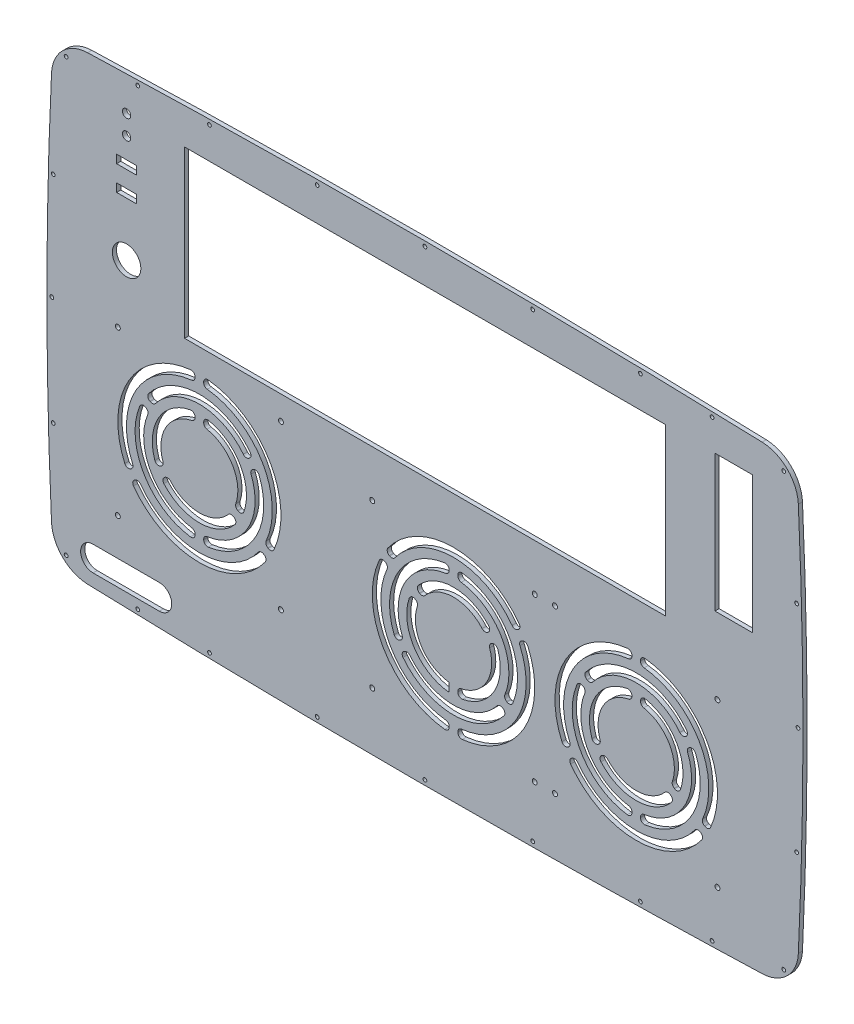
SolidWorks part; units mm, degrees
ref_plane "Front" through (0, 0, 0) normal (0, 0, 1) x (1, 0, 0)
ref_plane "Top" through (0, 0, 0) normal (0, 1, 0) x (1, 0, 0)
ref_plane "Right" through (0, 0, 0) normal (1, 0, 0) x (0, 0, -1)
sketch "Sketch1" plane through (0, 0, 0) normal (0, 0, 1) x (1, 0, 0)
  line L0 (79.622, -180.7786) -> (85.5592, -180.7149)
  line L1 (223.1034, -177.9577) -> (258.4236, -176.8528)
  circle A0 centre (-274.9542, -165.9116) radius 1.435
  arc A93 (-279.7814, -166.2105) -> (-275.1845, -170.7425) centre (-257.4604, -148.1676) ccw
  arc A94 (275.1845, -170.7425) -> (279.7814, -166.2105) centre (257.4604, -148.1676) ccw
  circle A100 centre (-274.9542, 164.9337) radius 1.4351
  circle A101 centre (-284.8103, 82.061) radius 1.4351
  circle A102 centre (-285.9024, 0) radius 1.4351
  circle A103 centre (-284.8103, -83.0389) radius 1.4351
  arc A104 (-258.4236, -176.8528) -> (-223.1034, -177.9577) centre (0, 7519.4009) ccw
  circle A105 centre (-220.0271, -174.2607) radius 1.4351
  circle A106 centre (-165.1, -175.6347) radius 1.4351
  arc A107 (-162.2131, -179.4816) -> (-85.5592, -180.7149) centre (0, 7519.4009) ccw
  arc A108 (-168.1492, -179.3542) -> (-162.2131, -179.4816) centre (0, 7519.4009) ccw
  circle A109 centre (-82.55, -176.963) radius 1.4351
  circle A110 centre (0, -177.4057) radius 1.4351
  circle A111 centre (82.55, -176.963) radius 1.4351
  circle A112 centre (165.1, -175.6347) radius 1.4351
  circle A113 centre (220.0271, -174.2607) radius 1.4351
  circle A114 centre (284.8103, -83.0389) radius 1.4351
  circle A115 centre (285.9024, 0) radius 1.4351
  circle A116 centre (284.8103, 82.061) radius 1.4351
  circle A117 centre (274.9542, 164.9337) radius 1.4351
  circle A118 centre (220.0271, 173.2828) radius 1.4351
  circle A119 centre (165.1, 174.6568) radius 1.4351
  circle A120 centre (82.55, 175.9851) radius 1.4351
  circle A121 centre (0, 176.4278) radius 1.4351
  circle A122 centre (-82.55, 175.9851) radius 1.4351
  circle A123 centre (-220.0271, 173.2828) radius 1.4351
  circle A124 centre (-165.1, 174.6568) radius 1.4351
  arc A125 (-162.2131, 178.5037) -> (-168.1492, 178.3763) centre (0, -7520.3788) ccw
  arc A126 (-85.5592, 179.737) -> (-162.2131, 178.5037) centre (0, -7520.3788) ccw
  arc A127 (-79.622, 179.8007) -> (-85.5592, 179.737) centre (0, -7520.3788) ccw
  arc A128 (-2.9688, 180.2118) -> (-79.622, 179.8007) centre (0, -7520.3788) ccw
  arc A129 (2.9688, 180.2118) -> (-2.9688, 180.2118) centre (0, -7520.3788) ccw
  arc A130 (79.622, 179.8007) -> (2.9688, 180.2118) centre (0, -7520.3788) ccw
  arc A131 (85.5592, 179.737) -> (79.622, 179.8007) centre (0, -7520.3788) ccw
  arc A132 (162.2131, 178.5037) -> (85.5592, 179.737) centre (0, -7520.3788) ccw
  arc A133 (168.1492, 178.3763) -> (162.2131, 178.5037) centre (0, -7520.3788) ccw
  arc A134 (217.1671, 177.1496) -> (168.1492, 178.3763) centre (0, -7520.3788) ccw
  arc A135 (223.1034, 176.9798) -> (217.1671, 177.1496) centre (0, -7520.3788) ccw
  arc A136 (258.4236, 175.8749) -> (223.1034, 176.9798) centre (0, -7520.3788) ccw
  arc A137 (275.1845, 169.7646) -> (258.4236, 175.8749) centre (257.4604, 147.1897) ccw
  arc A138 (279.7814, 165.2326) -> (275.1845, 169.7646) centre (257.4604, 147.1897) ccw
  arc A139 (286.1291, 148.559) -> (279.7814, 165.2326) centre (257.4604, 147.1897) ccw
  arc A140 (288.513, 85.1308) -> (286.1291, 148.559) centre (-2834.64, -0.4889) ccw
  arc A141 (288.6701, 79.1915) -> (288.513, 85.1308) centre (-2834.64, -0.4889) ccw
  arc A142 (289.6845, 2.9713) -> (288.6701, 79.1915) centre (-2834.64, -0.4889) ccw
  arc A143 (289.6854, -2.9701) -> (289.6845, 2.9713) centre (-2834.64, -0.4889) ccw
  arc A144 (288.6701, -80.1694) -> (289.6854, -2.9701) centre (-2834.64, -0.4889) ccw
  arc A145 (288.513, -86.1087) -> (288.6701, -80.1694) centre (-2834.64, -0.4889) ccw
  arc A146 (286.1291, -149.5369) -> (288.513, -86.1087) centre (-2834.64, -0.4889) ccw
  arc A147 (279.7814, -166.2105) -> (286.1291, -149.5369) centre (257.4604, -148.1676) ccw
  arc A148 (275.1845, -170.7425) -> (279.7814, -166.2105) centre (257.4604, -148.1676) ccw
  arc A149 (258.4236, -176.8528) -> (275.1845, -170.7425) centre (257.4604, -148.1676) ccw
  arc A150 (217.1671, -178.1275) -> (223.1034, -177.9577) centre (0, 7519.4009) ccw
  arc A151 (168.1492, -179.3542) -> (217.1671, -178.1275) centre (0, 7519.4009) ccw
  arc A152 (85.5592, -180.7149) -> (162.2131, -179.4816) centre (0, 7519.4009) ccw
  arc A153 (162.2131, -179.4816) -> (168.1492, -179.3542) centre (0, 7519.4009) ccw
  arc A154 (2.9688, -181.1897) -> (79.622, -180.7786) centre (0, 7519.4009) ccw
  arc A155 (-2.9688, -181.1897) -> (2.9688, -181.1897) centre (0, 7519.4009) ccw
  arc A156 (-79.622, -180.7786) -> (-2.9688, -181.1897) centre (0, 7519.4009) ccw
  arc A157 (-85.5592, -180.7149) -> (-79.622, -180.7786) centre (0, 7519.4009) ccw
  arc A158 (-217.1671, -178.1275) -> (-168.1492, -179.3542) centre (0, 7519.4009) ccw
  arc A159 (-223.1034, -177.9577) -> (-217.1671, -178.1275) centre (0, 7519.4009) ccw
  arc A160 (-275.1845, -170.7425) -> (-258.4236, -176.8528) centre (-257.4604, -148.1676) ccw
  arc A161 (-279.7814, -166.2105) -> (-275.1845, -170.7425) centre (-257.4604, -148.1676) ccw
  arc A162 (-286.1291, -149.5369) -> (-279.7814, -166.2105) centre (-257.4604, -148.1676) ccw
  arc A163 (-288.513, -86.1087) -> (-286.1291, -149.5369) centre (2834.64, -0.4889) ccw
  arc A164 (-288.6701, -80.1694) -> (-288.513, -86.1087) centre (2834.64, -0.4889) ccw
  arc A165 (-289.6854, -2.9701) -> (-288.6701, -80.1694) centre (2834.64, -0.4889) ccw
  arc A166 (-289.6845, 2.9713) -> (-289.6854, -2.9701) centre (2834.64, -0.4889) ccw
  arc A167 (-288.6701, 79.1915) -> (-289.6845, 2.9713) centre (2834.64, -0.4889) ccw
  arc A168 (-288.513, 85.1308) -> (-288.6701, 79.1915) centre (2834.64, -0.4889) ccw
  arc A169 (-286.1291, 148.559) -> (-288.513, 85.1308) centre (2834.64, -0.4889) ccw
  arc A170 (-279.7814, 165.2326) -> (-286.1291, 148.559) centre (-257.4604, 147.1897) ccw
  arc A171 (-275.1845, 169.7646) -> (-279.7814, 165.2326) centre (-257.4604, 147.1897) ccw
  arc A172 (-258.4236, 175.8749) -> (-275.1845, 169.7646) centre (-257.4604, 147.1897) ccw
  arc A173 (-223.1034, 176.9798) -> (-258.4236, 175.8749) centre (0, -7520.3788) ccw
  arc A174 (-217.1671, 177.1496) -> (-223.1034, 176.9798) centre (0, -7520.3788) ccw
  arc A175 (-168.1492, 178.3763) -> (-217.1671, 177.1496) centre (0, -7520.3788) ccw
  circle A176 centre (274.9542, -165.9116) radius 1.4351
extrude "Boss-Extrude1" add sketch "Sketch1" along normal blind 3.175 contours A125 A175 A174 A173 A172 A171 A170 A169 A168 A167 A166 A165 A164 A163 A162 A160 A104 A159 A158 A108 A107 A157 A156 A155 A154 L0 A152 A153 A151 A150 L1 A149 A147 A146 A145 A144 A143 A142 A141 A140 A139 region at (-0.0006, -0.4886, 0)
sketch "Sketch2" plane through (0, 0, 3.175) normal (0, 0, 1) x (1, 0, 0)
  line L0 (-184.15, 150.4749) -> (-184.15, 23.4749)
  line L1 (184.15, 23.4749) -> (-184.15, 23.4749)
  line L2 (184.15, 23.4749) -> (184.15, 150.4749)
  line L3 (184.15, 150.4749) -> (-184.15, 150.4749)
  line L4 (0, 23.4749) -> (0, 150.4749) construction
  line L5 (0, -177.4057) -> (0, 176.4278) construction
  arc A0 (258.4236, 175.8749) -> (-258.4236, 175.8749) centre (0, -7520.3788) ccw construction
  arc A1 (258.4236, 175.8749) -> (-258.4236, 175.8749) centre (0, -7520.3788) ccw
  dimension "D1" = 25.4
  dimension "D3" = 127
  dimension "D4" = 368.3
extrude "Cut-Extrude1" cut sketch "Sketch2" against normal through all contours L2 L3 L0 L1 region at (0, 86.9749, 3.175)
sketch "Sketch4" plane through (212.7609, -112.7514, 0) normal (0, 0, -1) x (0, -1, 0)
  circle A0 centre (-100.5499, 253.1068) radius 1.8986
  circle A1 centre (23.9501, 253.1068) radius 1.8987
  circle A2 centre (-100.5499, 128.6068) radius 1.8987
  circle A3 centre (-100.5499, 113.1068) radius 1.8987
  circle A4 centre (23.9501, 128.6068) radius 1.8987
  circle A5 centre (23.9501, 113.1068) radius 1.8987
  circle A6 centre (-100.5499, -11.3932) radius 1.8987
  circle A7 centre (23.9501, -11.3932) radius 1.8987
  circle A8 centre (53.1601, -62.1932) radius 1.4351 construction
  circle A10 centre (53.1601, -62.1932) radius 1.4351 construction
  dimension "D7" = 3.7973
  dimension "D1" = 124.5
  dimension "D2" = 124.5
  dimension "D3" = 140
  dimension "D4" = 264.5
  dimension "D5" = 29.21
  dimension "D6" = 50.8
extrude "Cut-Extrude2" cut sketch "Sketch4" against normal through all
sketch "Sketch5" plane through (0, 0, 0) normal (0, 0, -1) x (-1, 0, 0)
  circle A0 centre (235.3291, -119.7028) radius 1.8987
  circle A1 centre (110.3291, -119.7028) radius 1.8987
  circle A2 centre (110.3291, 5.2972) radius 1.8987
  circle A3 centre (235.3291, 5.2972) radius 1.8987
  dimension "D1" = 3.7973
  dimension "D4" = 50.8
  dimension "D2" = 125
  dimension "D3" = 125
  dimension "D5" = 57.15
extrude "Cut-Extrude3" cut sketch "Sketch5" against normal through all
sketch "Sketch6" plane through (0, 0, 0) normal (0, 0, -1) x (-1, 0, 0)
  line L1 (184.15, 150.4749) -> (184.15, 23.4749) construction
  line L2 (-184.15, 150.4749) -> (184.15, 150.4749) construction
  line L3 (220.98, 119.6647) -> (236.22, 119.6647)
  line L4 (220.98, 119.6647) -> (220.98, 113.3147)
  line L5 (220.98, 113.3147) -> (236.22, 113.3147)
  line L6 (236.22, 119.6647) -> (236.22, 113.3147)
  line L7 (220.98, 119.6647) -> (236.22, 113.3147) construction
  line L8 (220.98, 113.3147) -> (236.22, 119.6647) construction
  line L9 (220.98, 100.6147) -> (236.22, 100.6147)
  line L10 (220.98, 100.6147) -> (220.98, 94.2647)
  line L11 (220.98, 94.2647) -> (236.22, 94.2647)
  line L12 (236.22, 100.6147) -> (236.22, 94.2647)
  line L13 (220.98, 100.6147) -> (236.22, 94.2647) construction
  line L14 (220.98, 94.2647) -> (236.22, 100.6147) construction
  line L15 (-250.825, 150.4749) -> (-222.25, 150.4749)
  line L16 (-250.825, 150.4749) -> (-250.825, 45.6999)
  line L17 (-250.825, 45.6999) -> (-222.25, 45.6999)
  line L18 (-222.25, 150.4749) -> (-222.25, 45.6999)
  line L19 (-184.15, 23.4749) -> (-184.15, 150.4749) construction
  circle A0 centre (228.6, 150.4749) radius 3.175
  circle A1 centre (228.6, 135.5397) radius 3.175
  point P4 (228.6, 97.4397)
  point P12 (228.6, 116.4897)
  dimension "D1" = 6.35
  dimension "D8" = 104.775
  dimension "D2" = 14.9352
  dimension "D3" = 44.45
  dimension "D4" = 19.05
  dimension "D5" = 19.05
  dimension "D6" = 6.35
  dimension "D7" = 15.24
  dimension "D9" = 28.575
  dimension "D10" = 38.1
extrude "Cut-Extrude4" cut sketch "Sketch6" against normal through all contours L16 L15 L18 L17 | L4 L3 L6 L5 | A1 | A0 | L10 L9 L12 L11
sketch "Sketch7" plane through (0, 0, 0) normal (0, 0, -1) x (-1, 0, 0)
  line L0 (220.98, 94.2647) -> (236.22, 94.2647) construction
  circle A0 centre (228.6, 52.9897) radius 10.922
  point P2 (228.6, 135.5397)
  dimension "D1" = 21.844
  dimension "D2" = 41.275
extrude "Cut-Extrude5" cut sketch "Sketch7" against normal through all contours A0
sketch "Sketch8" plane through (0, 0, 0) normal (0, 0, -1) x (-1, 0, 0)
  line L0 (-224.1542, -12.2016) -> (-99.6542, -12.2016) construction
  line L1 (-84.1542, -12.2016) -> (40.3458, -12.2016) construction
  line L2 (40.3458, -12.2016) -> (40.3458, -136.7016) construction
  line L3 (-161.9042, -12.2016) -> (-161.9042, -18.8056) construction
  line L4 (-165.2062, -12.2892) -> (-165.2062, -18.9036)
  line L5 (-158.6022, -12.2892) -> (-158.6022, -18.9036)
  line L6 (-125.1518, -53.2326) -> (-119.4325, -49.9306) construction
  line L7 (-121.1799, -47.1266) -> (-126.9142, -50.4373)
  line L8 (-117.8779, -52.8458) -> (-123.6122, -56.1565)
  line L9 (-136.5902, -89.0666) -> (-130.871, -92.3686) construction
  line L10 (-129.352, -89.4327) -> (-135.1013, -86.1134)
  line L11 (-132.654, -95.152) -> (-138.4033, -91.8326)
  line L12 (-106.419, -102.6731) -> (-112.1472, -99.3659)
  line L13 (-107.9941, -105.5766) -> (-113.7133, -102.2746) construction
  line L14 (-109.721, -108.3924) -> (-115.4492, -105.0852)
  line L15 (-158.6022, -123.3823) -> (-158.6022, -116.7609)
  line L16 (-161.9042, -116.8896) -> (-161.9042, -123.4936) construction
  line L17 (-165.2062, -123.3823) -> (-165.2062, -116.7609)
  line L18 (-191.1543, -95.152) -> (-185.405, -91.8326)
  line L19 (-187.2181, -89.0666) -> (-192.9373, -92.3686) construction
  line L20 (-194.4563, -89.4327) -> (-188.707, -86.1134)
  line L21 (-214.0873, -108.3924) -> (-208.3591, -105.0852)
  line L22 (-215.8142, -105.5766) -> (-210.095, -102.2746) construction
  line L23 (-217.3893, -102.6731) -> (-211.6611, -99.3659)
  line L24 (-205.9304, -52.8458) -> (-200.1961, -56.1565)
  line L25 (-198.6565, -53.2326) -> (-204.3758, -49.9306) construction
  line L26 (-202.6284, -47.1266) -> (-196.8941, -50.4373)
  line L27 (-165.2062, -38.77) -> (-165.2062, -45.4087)
  line L28 (-161.9042, -45.2216) -> (-161.9042, -38.6176) construction
  line L29 (-158.6022, -38.77) -> (-158.6022, -45.4087)
  line L30 (-84.1542, -136.7016) -> (-99.6542, -12.2016) construction
  line L31 (-18.6022, -136.6139) -> (-18.6022, -129.9995)
  line L32 (-25.2062, -136.6139) -> (-25.2062, -129.9995)
  line L33 (-62.6284, -101.7765) -> (-56.8941, -98.4659)
  line L34 (-65.9304, -96.0573) -> (-60.1961, -92.7466)
  line L35 (-54.4563, -59.4704) -> (-48.707, -62.7897)
  line L36 (-51.1543, -53.7512) -> (-45.405, -57.0705)
  line L37 (-77.3893, -46.23) -> (-71.6611, -49.5372)
  line L38 (-74.0873, -40.5108) -> (-68.3591, -43.818)
  line L39 (-25.2062, -25.5209) -> (-25.2062, -32.1422)
  line L40 (-18.6022, -25.5209) -> (-18.6022, -32.1422)
  line L41 (7.346, -53.7512) -> (1.5967, -57.0705)
  line L42 (10.648, -59.4704) -> (4.8987, -62.7897)
  line L43 (30.279, -40.5108) -> (24.5508, -43.818)
  line L44 (33.581, -46.23) -> (27.8528, -49.5372)
  line L45 (22.1221, -96.0573) -> (16.3878, -92.7466)
  line L46 (18.8201, -101.7765) -> (13.0858, -98.4659)
  line L47 (-18.6022, -110.1331) -> (-18.6022, -103.4945)
  line L48 (-25.2062, -110.1331) -> (-25.2062, -103.4945)
  line L49 (40.3458, -136.7016) -> (-84.1542, -136.7016) construction
  line L50 (-21.9042, -136.7016) -> (-21.9042, -130.0976) construction
  line L51 (-58.6565, -95.6706) -> (-64.3758, -98.9726) construction
  line L52 (-47.2181, -59.8366) -> (-52.9373, -56.5346) construction
  line L53 (-75.8142, -43.3266) -> (-70.095, -46.6286) construction
  line L54 (-21.9042, -32.0136) -> (-21.9042, -25.4096) construction
  line L55 (3.4098, -59.8366) -> (9.129, -56.5346) construction
  line L56 (32.0059, -43.3266) -> (26.2867, -46.6286) construction
  line L57 (14.8482, -95.6706) -> (20.5675, -98.9726) construction
  line L58 (-21.9042, -103.6816) -> (-21.9042, -110.2856) construction
  line L59 (-99.6542, -12.2016) -> (-84.1542, -136.7016) construction
  line L60 (-91.9042, -74.4516) -> (-106.419, -102.6731) construction
  line L91 (-250.825, 150.4749) -> (-250.825, 45.6999) construction
  line L92 (-250.825, 150.4749) -> (-222.25, 150.4749) construction
  circle A0 centre (-161.9042, -74.4516) radius 62.25
  circle A1 centre (-161.9042, -74.4516) radius 55.646
  circle A2 centre (-161.9042, -74.4516) radius 49.042
  circle A3 centre (-161.9042, -74.4516) radius 42.438
  circle A4 centre (-161.9042, -74.4516) radius 35.834
  circle A5 centre (-161.9042, -74.4516) radius 29.23
  circle A6 centre (-161.9042, -74.4516) radius 22.626
  circle A7 centre (-21.9042, -74.4516) radius 62.25
  circle A8 centre (-21.9042, -74.4516) radius 55.646
  circle A9 centre (-21.9042, -74.4516) radius 49.042
  circle A10 centre (-21.9042, -74.4516) radius 42.438
  circle A11 centre (-21.9042, -74.4516) radius 35.834
  circle A12 centre (-21.9042, -74.4516) radius 29.23
  circle A13 centre (-21.9042, -74.4516) radius 22.626
  point P0 (-161.9042, -74.4516)
  point P1 (-21.9042, -74.4516)
  point P10 (-161.9042, -12.2016)
  point P11 (-21.9042, -12.2016)
  point P14 (40.3458, -74.4516)
  point P29 (-91.9042, -74.4516)
  point P86 (-161.9042, -74.4516)
  point P89 (-21.9042, -74.4516)
  point P92 (-21.9042, -136.7016)
  point P162 (-21.9042, -74.4516)
  dimension "D7" = 3.302
  dimension "D8" = 6.604
  dimension "D9" = 60
  dimension "D10" = 3.302
  dimension "D11" = 6.604
  dimension "D12" = 60
  dimension "D13" = 3.302
  dimension "D14" = 6.604
  dimension "D17" = 31.7354
  dimension "D1" = 6.604
  dimension "D2" = 6.604
  dimension "D3" = 6.604
  dimension "D4" = 6.604
  dimension "D5" = 6.604
  dimension "D6" = 6.604
  dimension "D15" = 3
  dimension "D16" = 2
extrude "Cut-Extrude8" cut sketch "Sketch8" against normal through all contours A1 L4 A0 L23 | A1 L12 A0 L5 | A1 L21 A0 L14 | A3 L24 A2 L17 | A3 L7 A2 L26 | A3 L15 A2 L8 | A5 L18 A4 L11 | A5 L10 A4 L29 | A5 L27 A4 L20 | A8 L43 A7 L38 | A10 L39 A9 L34 | A10 L45 A9 L40 | A8 L31 A7 L44 | A8 L37 A7 L32 | A10 L33 A9 L46 | A12 L35 A11 L48 | A12 L47 A11 L42 | A12 L41 A11 L36 region at (166.2852, -15.5964, 0) region at (117.5174, -32.36, 0) region at (210.678, -107.6832, 0) region at (124.4731, -48.044, 0) region at (114.9515, -63.5515, 0) region at (203.4836, -55.2292, 0) region at (131.9256, -87.2516, 0) region at (161.9042, -109.6722, 0) region at (192.4159, -56.8356, 0) region at (17.5231, -133.3067, 0) region at (74.8797, -105.037, 0) region at (21.9042, -13.2921, 0) region at (59.3352, -100.8591, 0) region at (63.6477, -50.3509, 0) region at (-19.6753, -93.6739, 0) region at (51.8827, -61.6515, 0) region at (21.9042, -39.231, 0) region at (18.0001, -106.8138, 0)
sketch "Sketch12" plane through (0, 0, 3.175) normal (0, 0, 1) x (1, 0, 0)
  line L0 (-170.4885, 5.2972) -> (-175.1698, 5.2972) construction
  line L3 (-172.8291, 5.2972) -> (-172.8291, -1.3068) construction
  line L4 (-176.1311, 5.2099) -> (-176.1311, -1.4045)
  line L5 (-169.5271, 5.2099) -> (-169.5271, -1.4045)
  line L6 (-135.8602, -35.8588) -> (-130.141, -32.5568) construction
  line L7 (-131.8879, -29.7526) -> (-137.622, -33.0632)
  line L8 (-128.5859, -35.4718) -> (-134.32, -38.7824)
  line L9 (-147.2987, -71.9428) -> (-141.5795, -75.2448) construction
  line L10 (-140.0596, -72.3095) -> (-145.8084, -68.9905)
  line L11 (-143.3616, -78.0288) -> (-149.1104, -74.7097)
  line L12 (-117.1271, -85.5496) -> (-122.8553, -82.2424)
  line L13 (-118.7025, -88.4528) -> (-124.4218, -85.1508) construction
  line L14 (-120.4291, -91.2688) -> (-126.1573, -87.9616)
  line L15 (-169.5271, -106.3841) -> (-169.5271, -99.7629)
  line L16 (-172.8291, -99.8908) -> (-172.8291, -106.4948) construction
  line L17 (-176.1311, -106.3841) -> (-176.1311, -99.7629)
  line L18 (-202.2967, -78.0288) -> (-196.5479, -74.7097)
  line L19 (-198.3596, -71.9428) -> (-204.0788, -75.2448) construction
  line L20 (-205.5987, -72.3095) -> (-199.8499, -68.9905)
  line L21 (-225.2291, -91.2688) -> (-219.5009, -87.9616)
  line L22 (-226.9557, -88.4528) -> (-221.2365, -85.1508) construction
  line L23 (-228.5311, -85.5496) -> (-222.8029, -82.2424)
  line L24 (-217.0724, -35.4718) -> (-211.3383, -38.7824)
  line L25 (-209.798, -35.8588) -> (-215.5173, -32.5568) construction
  line L26 (-213.7704, -29.7526) -> (-208.0363, -33.0632)
  line L27 (-176.1311, -21.2702) -> (-176.1311, -27.9083)
  line L28 (-172.8291, -27.7228) -> (-172.8291, -21.1188) construction
  line L29 (-169.5271, -21.2702) -> (-169.5271, -27.9083)
  line L61 (-235.3291, 5.2972) -> (-110.3291, 5.2972) construction
  line L62 (-235.3291, -119.7028) -> (-110.3291, -119.7028) construction
  line L63 (-235.3291, 5.2972) -> (-235.3291, -119.7028) construction
  circle A0 centre (-172.8291, -57.2028) radius 62.5
  circle A1 centre (-172.8291, -57.2028) radius 55.896
  circle A2 centre (-172.8291, -57.2028) radius 49.292
  circle A3 centre (-172.8291, -57.2028) radius 42.688
  circle A4 centre (-172.8291, -57.2028) radius 36.084
  circle A5 centre (-172.8291, -57.2028) radius 29.48
  circle A6 centre (-172.8291, -57.2028) radius 22.876
  point P0 (-172.8291, -57.2028)
  point P10 (-172.8291, 5.2972)
  point P86 (-172.8291, -57.2028)
  dimension "D7" = 3.302
  dimension "D8" = 6.604
  dimension "D9" = 60
  dimension "D10" = 3.302
  dimension "D11" = 6.604
  dimension "D12" = 60
  dimension "D13" = 3.302
  dimension "D14" = 6.604
  dimension "D1" = 6.604
  dimension "D2" = 6.604
  dimension "D3" = 6.604
  dimension "D4" = 6.604
  dimension "D5" = 6.604
  dimension "D6" = 6.604
  dimension "D15" = 3
extrude "Cut-Extrude9" cut sketch "Sketch12" against normal through all contours A1 L4 A0 L23 | A1 L12 A0 L5 | A3 L7 A2 L26 | A5 L27 A4 L20 | A5 L10 A4 L29 | A3 L15 A2 L8 | A1 L21 A0 L14 | A5 L18 A4 L11 | A3 L24 A2 L17 region at (-177.2147, 1.9027, 3.175) region at (-128.2687, -14.9376, 3.175) region at (-221.8175, -90.5635, 3.175) region at (-135.1832, -30.6661, 3.175) region at (-125.6392, -46.2392, 3.175) region at (-214.6279, -37.8591, 3.175) region at (-142.6307, -70.1247, 3.175) region at (-172.8291, -92.6689, 3.175) region at (-203.5535, -39.4641, 3.175)
fillet "Fillet4" radius 3.048 106 edges at (123.6122, -56.1565, 1.5875) (158.6022, -45.4087, 1.5875) (165.2062, -38.77, 1.5875) (165.2062, -45.4087, 1.5875) (158.6022, -38.77, 1.5875) (165.2062, -12.2892, 1.5875) (121.1799, -47.1266, 1.5875) (126.9142, -50.4373, 1.5875) (117.8779, -52.8458, 1.5875) (135.1013, -86.1134, 1.5875) (129.352, -89.4327, 1.5875) (112.1472, -99.3659, 1.5875) (106.419, -102.6731, 1.5875) (109.721, -108.3924, 1.5875) (115.4492, -105.0852, 1.5875) (158.6022, -123.3823, 1.5875) (158.6022, -116.7609, 1.5875) (132.654, -95.152, 1.5875) (138.4033, -91.8326, 1.5875) (185.405, -91.8326, 1.5875) (191.1543, -95.152, 1.5875) (165.2062, -123.3823, 1.5875) (165.2062, -116.7609, 1.5875) (214.0873, -108.3924, 1.5875) (208.3591, -105.0852, 1.5875) (217.3893, -102.6731, 1.5875) (211.6611, -99.3659, 1.5875) (194.4563, -89.4327, 1.5875) (188.707, -86.1134, 1.5875) (205.9304, -52.8458, 1.5875) (200.1961, -56.1565, 1.5875) (202.6284, -47.1266, 1.5875) (196.8941, -50.4373, 1.5875) (165.2062, -18.9036, 1.5875) (158.6022, -18.9036, 1.5875) (158.6022, -12.2892, 1.5875) (-134.32, -38.7824, 1.5875) (-128.5859, -35.4718, 1.5875) (-137.622, -33.0632, 1.5875) (-131.8879, -29.7526, 1.5875) (-169.5271, 5.2099, 1.5875) (-169.5271, -1.4045, 1.5875) (-176.1311, -1.4045, 1.5875) (-176.1311, 5.2099, 1.5875) (-169.5271, -21.2702, 1.5875) (-169.5271, -27.9083, 1.5875) (-176.1311, -27.9083, 1.5875) (-176.1311, -21.2702, 1.5875) (-208.0363, -33.0632, 1.5875) (-211.3383, -38.7824, 1.5875) (-213.7704, -29.7526, 1.5875) (-217.0724, -35.4718, 1.5875) (-225.2291, -91.2688, 1.5875) (-219.5009, -87.9616, 1.5875) (-222.8029, -82.2424, 1.5875) (-228.5311, -85.5496, 1.5875) (-176.1311, -106.3841, 1.5875) (-176.1311, -99.7629, 1.5875) (-199.8499, -68.9905, 1.5875) (-205.5987, -72.3095, 1.5875) (-196.5479, -74.7097, 1.5875) (-202.2967, -78.0288, 1.5875) (-140.0596, -72.3095, 1.5875) (-145.8084, -68.9905, 1.5875) (-143.3616, -78.0288, 1.5875) (-149.1104, -74.7097, 1.5875) (-169.5271, -106.3841, 1.5875) (-169.5271, -99.7629, 1.5875) (-120.4291, -91.2688, 1.5875) (-117.1271, -85.5496, 1.5875) (-122.8553, -82.2424, 1.5875) (-126.1573, -87.9616, 1.5875) (54.4563, -59.4704, 1.5875) (48.707, -62.7897, 1.5875) (45.405, -57.0705, 1.5875) (51.1543, -53.7512, 1.5875) (-7.346, -53.7512, 1.5875) (-1.5967, -57.0705, 1.5875) (-4.8987, -62.7897, 1.5875) (-10.648, -59.4704, 1.5875) (-16.3878, -92.7466, 1.5875) (-22.1221, -96.0573, 1.5875) (-13.0858, -98.4659, 1.5875) (-18.8201, -101.7765, 1.5875) (25.2062, -136.6139, 1.5875) (18.6022, -136.6139, 1.5875) (18.6022, -129.9995, 1.5875) (25.2062, -129.9995, 1.5875) (25.2062, -103.4945, 1.5875) (25.2062, -110.1331, 1.5875) (56.8941, -98.4659, 1.5875) (62.6284, -101.7765, 1.5875) (65.9304, -96.0573, 1.5875) (60.1961, -92.7466, 1.5875) (71.6611, -49.5372, 1.5875) (77.3893, -46.23, 1.5875) (74.0873, -40.5108, 1.5875) (25.2062, -25.5209, 1.5875) (25.2062, -32.1422, 1.5875) (18.6022, -32.1422, 1.5875) (18.6022, -25.5209, 1.5875) (68.3591, -43.818, 1.5875) (-24.5508, -43.818, 1.5875) (-27.8528, -49.5372, 1.5875) (-30.279, -40.5108, 1.5875) (-33.581, -46.23, 1.5875)
sketch "Sketch13" plane through (0, 0, 3.175) normal (0, 0, 1) x (1, 0, 0)
  line L0 (-254.3171, -157.7507) -> (-203.5171, -157.7507) construction
  line L1 (-254.3171, -148.2257) -> (-203.5171, -148.2257)
  line L2 (-254.3171, -167.2757) -> (-203.5171, -167.2757)
  arc A0 (-254.3171, -148.2257) -> (-254.3171, -167.2757) centre (-254.3171, -157.7507) ccw
  arc A1 (-203.5171, -167.2757) -> (-203.5171, -148.2257) centre (-203.5171, -157.7507) ccw
  circle A3 centre (-220.0271, -174.2607) radius 1.4351 construction
  point P2 (-228.9171, -157.7507)
  dimension "D1" = 19.05
  dimension "D2" = 50.8
  dimension "D3" = 16.51
  dimension "D4" = 8.89
extrude "Cut-Extrude10" cut sketch "Sketch13" against normal through all
